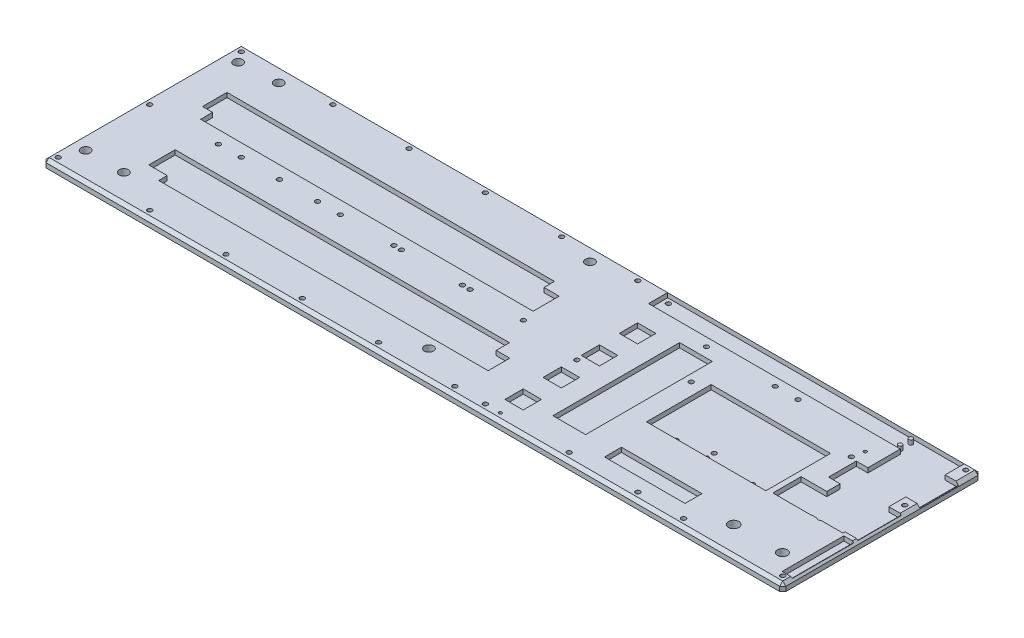
SolidWorks part; units mm, degrees
ref_plane "Front Plane" through (0, 0, 0) normal (0, 0, 1) x (1, 0, 0)
ref_plane "Top Plane" through (0, 0, 0) normal (0, 1, 0) x (1, 0, 0)
ref_plane "Right Plane" through (0, 0, 0) normal (1, 0, 0) x (0, 0, -1)
sketch "Sketch1" plane through (0, 0, 0) normal (0, 1, 0) x (1, 0, 0)
  line L1 (-180, 70) -> (305, 70)
  line L2 (-180, 70) -> (-180, -60)
  line L3 (-180, -60) -> (305, -60)
  line L4 (305, 70) -> (305, -60)
extrude "Boss-Extrude1" add sketch "Sketch1" against normal blind 5 from offset 1.6 offset against normal yes
sketch "Sketch2" plane through (0, -1.6, 0) normal (0, 1, 0) x (1, 0, 0)
  line L0 (305, 70) -> (-180, 70) construction
  line L2 (-180, 70) -> (-180, -60) construction
  line L3 (-180, -60) -> (305, -60) construction
  circle A2 centre (-170, 58) radius 3
  circle A3 centre (-145.0116, 59.6) radius 3
  circle A4 centre (58.6, 60) radius 3
  circle A7 centre (300, -55) radius 1.5
  circle A8 centre (-170, -42) radius 3
  circle A9 centre (-145, -42) radius 3
  circle A10 centre (55.002, -42.0047) radius 3
  circle A11 centre (-175, 65) radius 1.5
  circle A12 centre (-115, 65) radius 1.5
  circle A13 centre (-65, 65) radius 1.5
  circle A14 centre (-15, 65) radius 1.5
  circle A15 centre (35, 65) radius 1.5
  circle A16 centre (85, 65) radius 1.5
  circle A17 centre (105, 65) radius 1.5
  circle A18 centre (300, 65) radius 1.5
  circle A19 centre (85, -55) radius 1.5
  circle A20 centre (105, -55) radius 1.5
  circle A21 centre (205, -55) radius 1.5
  circle A22 centre (235, -55) radius 1.5
  circle A23 centre (-175, -55) radius 1.5
  circle A24 centre (-115, -55) radius 1.5
  circle A25 centre (-65, -55) radius 1.5
  circle A26 centre (-15, -55) radius 1.5
  circle A27 centre (35, -55) radius 1.5
  circle A28 centre (-175, 5) radius 1.5
  circle A31 centre (110, 0) radius 1.5
  circle A34 centre (205, -5) radius 1.5
  circle A35 centre (145, 50) radius 1.5
  circle A36 centre (190, 50) radius 1.5
  circle A37 centre (300, 25) radius 1.5
  circle A42 centre (159.99, -55.0047) radius 1.5
  circle A43 centre (204.99, 49.9953) radius 1.5
  circle A44 centre (159.99, 24.9953) radius 1.5
  circle A45 centre (184.99, -10.0047) radius 1.5
  circle A46 centre (204.99, -10.0047) radius 1.5
  circle A47 centre (235, -10.0047) radius 1.51
  circle A48 centre (279.8382, -10.0047) radius 1.6518
  circle A49 centre (114.99, -55.1047) radius 1
  circle A50 centre (286.79, -42.0047) radius 3.25
  circle A51 centre (254.8159, -42.0047) radius 3.4242
  circle A52 centre (254.99, 34.9953) radius 1.5
  circle A53 centre (256.59, 42.4953) radius 1
  circle A54 centre (-130.01, 4.9953) radius 1.5
  circle A55 centre (69.99, 4.9953) radius 1.5
  circle A56 centre (35, 4.9953) radius 1.51
  circle A57 centre (29.99, 4.9953) radius 1.5
  circle A58 centre (-10.01, 4.9953) radius 1.5
  circle A59 centre (-15, 4.9953) radius 1.51
  circle A60 centre (-50.01, 4.9953) radius 1.5
  circle A61 centre (-65, 4.9953) radius 1.51
  circle A62 centre (-115.01, 4.9953) radius 1.5
  circle A63 centre (-89.9834, 4.9953) radius 1.5266
  dimension "D3" = 3
  dimension "D4" = 20
  dimension "D5" = 265
  dimension "D6" = 12
  dimension "D7" = 10.4
  dimension "D8" = 10
  dimension "D9" = 18
  dimension "D10" = 25
extrude "Cut-Extrude1" cut sketch "Sketch2" against normal through all
sketch "Sketch3" plane through (0, -1.6, 0) normal (0, 1, 0) x (1, 0, 0)
  line L0 (305, 70) -> (-180, 70) construction
  line L3 (266.5908, 55.503) -> (303.9819, 55.503)
  line L4 (266.5908, 55.503) -> (266.5908, 30.0739)
  line L5 (266.5908, 30.0739) -> (303.9819, 30.0739)
  line L6 (303.9819, 55.503) -> (303.9819, 30.0739)
  line L7 (288.3592, 18.9249) -> (303.1307, 18.9249)
  line L8 (288.3592, 18.9249) -> (288.3592, -9.6619)
  line L9 (288.3592, -9.6619) -> (303.1307, -9.6619)
  line L10 (303.1307, 18.9249) -> (303.1307, -9.6619)
  line L11 (297.3726, -12.3054) -> (303.1307, -12.3054)
  line L12 (297.3726, -12.3054) -> (297.3726, -52.7789)
  line L13 (297.3726, -52.7789) -> (303.1307, -52.7789)
  line L14 (303.1307, -12.3054) -> (303.1307, -52.7789)
  line L27 (108.8347, 41) -> (120.8347, 41)
  line L28 (108.8347, 41) -> (108.8347, 29)
  line L29 (108.8347, 29) -> (120.8347, 29)
  line L30 (120.8347, 41) -> (120.8347, 29)
  line L35 (133.8233, 43.5526) -> (139.6368, 43.5526)
  line L36 (133.8233, 43.5526) -> (133.8233, -39.498)
  line L37 (133.8233, -39.498) -> (139.6368, -39.498)
  line L39 (149.7413, 43.5526) -> (155.278, 43.5526)
  line L41 (149.7413, -39.498) -> (155.278, -39.498)
  line L42 (155.278, 43.5526) -> (155.278, -39.498)
  line L47 (108.8347, 16) -> (120.8347, 16)
  line L48 (108.8347, 16) -> (108.8347, 4)
  line L49 (108.8347, 4) -> (120.8347, 4)
  line L50 (120.8347, 16) -> (120.8347, 4)
  line L51 (108.8347, -9) -> (120.8347, -9)
  line L52 (108.8347, -9) -> (108.8347, -21)
  line L53 (108.8347, -21) -> (120.8347, -21)
  line L54 (120.8347, -9) -> (120.8347, -21)
  line L55 (108.8347, -34) -> (120.8347, -34)
  line L56 (108.8347, -34) -> (108.8347, -46)
  line L57 (108.8347, -46) -> (120.8347, -46)
  line L58 (120.8347, -34) -> (120.8347, -46)
  line L69 (139.6368, 43.5526) -> (149.7413, 43.5526)
  line L71 (139.6368, -39.498) -> (149.7413, -39.498)
  line L72 (-156.6112, 37.2475) -> (58.0668, 37.2475)
  line L73 (-156.6112, 37.2475) -> (-156.6112, 21.188)
  line L74 (-156.6112, 21.188) -> (58.0668, 21.188)
  line L75 (58.0668, 37.2475) -> (58.0668, 21.188)
  line L76 (-141.024, -12.3054) -> (78.1412, -12.3054)
  line L77 (-141.024, -12.3054) -> (-141.024, -29.5884)
  line L78 (-141.024, -29.5884) -> (78.1412, -29.5884)
  line L79 (78.1412, -12.3054) -> (78.1412, -29.5884)
  line L80 (167.9681, 30.0739) -> (246.2247, 30.0739)
  line L81 (167.9681, 30.0739) -> (167.9681, -12.3054)
  line L82 (167.9681, -12.3054) -> (246.2247, -12.3054)
  line L83 (246.2247, 30.0739) -> (246.2247, -12.3054)
  line L84 (174.154, -34.9071) -> (226.9344, -34.9071)
  line L85 (174.154, -34.9071) -> (174.154, -46)
  line L86 (174.154, -46) -> (226.9344, -46)
  line L87 (226.9344, -34.9071) -> (226.9344, -46)
  line L88 (259.0115, 34.1925) -> (273.4659, 34.1925)
  line L89 (259.0115, 34.1925) -> (259.0115, 16)
  line L90 (259.0115, 16) -> (273.4659, 16)
  line L91 (273.4659, 34.1925) -> (273.4659, 16)
  line L92 (249.783, 7.2852) -> (274.9113, 7.2852)
  line L93 (249.783, 7.2852) -> (249.783, -11.2831)
  line L94 (249.783, -11.2831) -> (274.9113, -11.2831)
  line L95 (274.9113, 7.2852) -> (274.9113, -11.2831)
  line L96 (101.5059, 68.0736) -> (295.9696, 68.0736)
  line L97 (101.5059, 68.0736) -> (101.5059, 55.503)
  line L98 (101.5059, 55.503) -> (295.9696, 55.503)
  line L99 (295.9696, 68.0736) -> (295.9696, 55.503)
  circle A3 centre (264, 65) radius 1.3177
  circle A4 centre (264, 58) radius 1.3177
  dimension "D3" = 12
  dimension "D4" = 25
  dimension "D5" = 25
  dimension "D6" = 25
  dimension "D7" = 29
extrude "Cut-Extrude2" cut sketch "Sketch3" against normal blind 3 contours L99 L96 L97 L98 L3 A4 A3 | L88 L91 L5 L6 L3 L4 | L91 L88 L4 L5 | L91 L5 L4 L88 L89 L90 | L10 L7 L8 L9 | L95 L92 L93 L94 | L83 L80 L81 L82 | L87 L84 L85 L86 | L37 L71 L41 L42 L39 L69 L35 L36 | L75 L72 L73 L74 | L79 L76 L77 L78 | L30 L27 L28 L29 | L50 L47 L48 L49 | L54 L51 L52 L53 | L58 L55 L56 L57 | L14 L11 L12 L13 region at (198.4452, -1.6, -61.7896) region at (285.7547, -1.6, -43.1155) region at (270.0283, -1.6, -32.1332) region at (265.7814, -1.6, -24.2471) region at (295.7449, -1.6, -4.6315) region at (300.2517, -1.6, 32.5421) region at (114.8347, -1.6, -35) region at (144.5507, -1.6, -2.0273) region at (114.8347, -1.6, -10) region at (114.8347, -1.6, 15) region at (114.8347, -1.6, 40) region at (-49.2722, -1.6, -29.2178) region at (-31.4414, -1.6, 20.9469) region at (207.0964, -1.6, -8.8843) region at (200.5442, -1.6, 40.4535) region at (262.3471, -1.6, 1.9989)
chamfer "Chamfer1" distance 2 angle 45 8 edges at (-180, -4.1, -70) (305, -4.1, -70) (305, -4.1, 60) (-180, -4.1, 60) (-180, -1.6, -5) (62.5, -1.6, 60) (62.5, -1.6, -70) (305, -1.6, -5)
chamfer "Chamfer2" distance 1 angle 79 3 edges at (303.1307, -1.7307, -4.6315) (303.9819, -2.5819, -42.7885) (303.1307, -1.7307, 32.5421) first distance on face at (303.4054, -2.0054, -4.9695)
sketch "Sketch4" plane through (0, -6.6, 0) normal (0, -1, 0) x (1, 0, 0)
  circle A0 centre (-175, 55) radius 3.5
  circle A1 centre (-115, 55) radius 3.5
  circle A2 centre (-175, -5) radius 3.5
  circle A3 centre (-115, -5) radius 3.5
  circle A4 centre (-115, -65) radius 3.5
  circle A5 centre (-175, -65) radius 3.5
  circle A6 centre (-65, 55) radius 3.5
  circle A7 centre (-15, 55) radius 3.5
  circle A8 centre (35, 55) radius 3.5
  circle A9 centre (85, 55) radius 3.5
  circle A10 centre (105, 55) radius 3.5
  circle A11 centre (-65, -5) radius 3.5
  circle A12 centre (-15, -5) radius 3.5
  circle A13 centre (159.99, -24.9953) radius 3.5
  circle A14 centre (35, -65) radius 3.5
  circle A15 centre (-15, -65) radius 3.5
  circle A16 centre (-65, -65) radius 3.5
  circle A17 centre (85, -65) radius 3.5
  circle A18 centre (105, -65) radius 3.5
  circle A19 centre (110, 0) radius 3.5
  circle A20 centre (145, -50) radius 3.5
  circle A21 centre (190, -50) radius 3.5
  circle A22 centre (300, -65) radius 3.5
  circle A23 centre (300, 55) radius 3.5
  circle A24 centre (300, -25) radius 3.5
  circle A25 centre (205, 5) radius 3.5
  circle A26 centre (205, 55) radius 3.5
  circle A27 centre (235, 55) radius 3.5
  circle A28 centre (197.37, 10) radius 3.5
  circle A29 centre (160.54, 10) radius 3.5
  circle A30 centre (160.54, -28.1) radius 3.5
  circle A31 centre (197.37, -28.1) radius 3.5
  dimension "D1" = 7
extrude "Cut-Extrude3" cut sketch "Sketch4" against normal blind 3 rebuild error yes
sketch "Sketch5" plane through (0, -1.6, 0) normal (0, 1, 0) x (1, 0, 0)
  line L1 (-149.9612, 30.4267) -> (68.006, 30.4267)
  line L2 (-149.9612, 30.4267) -> (-149.9612, 13.3473)
  line L3 (-149.9612, 13.3473) -> (68.006, 13.3473)
  line L4 (68.006, 30.4267) -> (68.006, 13.3473)
  line L5 (-128.9322, -20.9775) -> (87.0323, -20.9775)
  line L6 (-128.9322, -20.9775) -> (-128.9322, -35.1528)
  line L7 (-128.9322, -35.1528) -> (87.0323, -35.1528)
  line L8 (87.0323, -20.9775) -> (87.0323, -35.1528)
  line L9 (266.5908, 30.0739) -> (295.5961, 30.0739)
  line L10 (266.5908, 30.0739) -> (266.5908, -11.071)
  line L11 (266.5908, -11.071) -> (295.5961, -11.071)
  line L12 (295.5961, 30.0739) -> (295.5961, -11.071)
extrude "Cut-Extrude5" cut sketch "Sketch5" against normal blind 3
